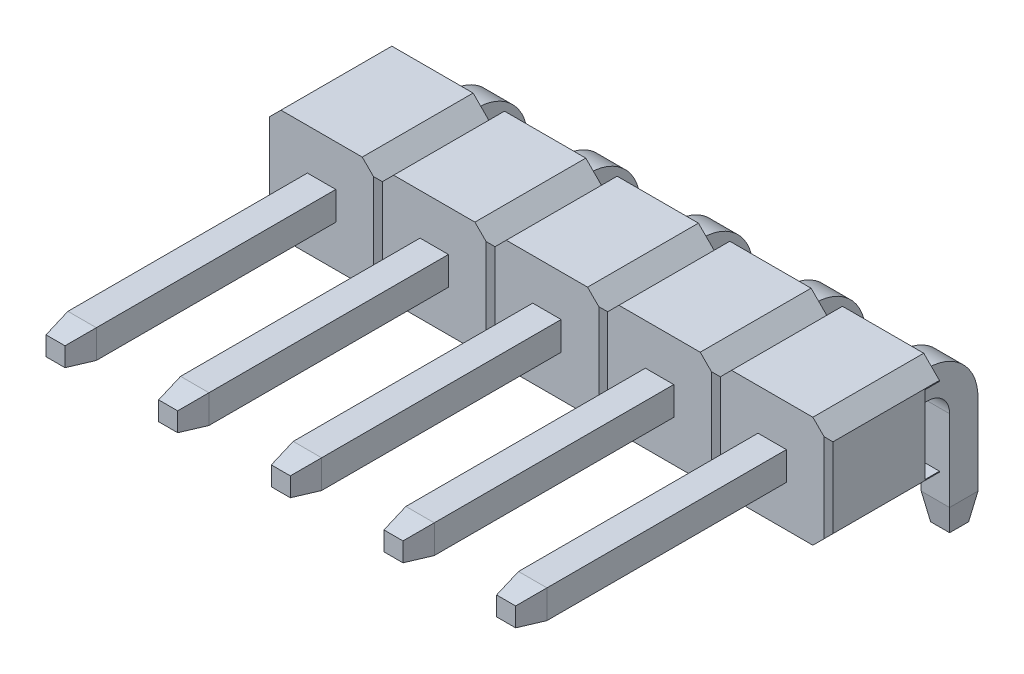
SolidWorks part; units mm, degrees
ref_plane "Front Plane" through (0, 0, 0) normal (0, 0, 1) x (1, 0, 0)
ref_plane "Top Plane" through (0, 0, 0) normal (0, 1, 0) x (1, 0, 0)
ref_plane "Right Plane" through (0, 0, 0) normal (1, 0, 0) x (0, 0, -1)
sketch "Sketch1" plane through (0, 0, 0) normal (0, 0, 1) x (1, 0, 0)
  line L0 (-1.27, 0.8964) -> (-0.9164, 1.25)
  line L1 (-0.9164, 1.25) -> (0.9164, 1.25)
  line L2 (-1.27, 0.8964) -> (-1.27, -0.8964)
  line L3 (-0.9164, -1.25) -> (0.9164, -1.25)
  line L4 (1.27, 0.8964) -> (1.27, -0.8964)
  line L5 (-1.27, -0.8964) -> (-0.9164, -1.25)
  line L6 (0.9164, -1.25) -> (1.27, -0.8964)
  line L7 (1.27, 0.8964) -> (0.9164, 1.25)
  point P0 (1.27, -1.25)
  point P7 (-1.27, 1.25)
  point P10 (-1.27, -1.25)
  point P15 (1.27, 1.25)
  dimension "D5" = 0.25
  dimension "D1" = 2.54
  dimension "D2" = 2.5
  dimension "D3" = 1.27
  dimension "D4" = 1.25
  dimension "D6" = 0.25
  dimension "D7" = 0.25
  dimension "D8" = 0.25
extrude "Extrude1" add sketch "Sketch1" along normal blind 1.25 and the other way blind 1.25
sketch "Sketch4" plane through (0, 0, 0) normal (0, 1, 0) x (1, 0, 0)
  line L0 (-1.27, -1.15) -> (-1.17, -1.25)
  line L1 (-1.17, -1.25) -> (-1.27, -1.25)
  line L2 (-1.27, -1.25) -> (-1.27, -1.15)
  line L3 (1.17, -1.25) -> (1.27, -1.15)
  line L4 (1.27, -1.15) -> (1.27, -1.25)
  line L5 (1.27, -1.25) -> (1.17, -1.25)
extrude "Cut-Extrude3" cut sketch "Sketch4" against normal through all and the other way through all
pattern_linear "LPattern4" count 3 spacing 2.54 along (-1, 0, 0) count 3 spacing 2.54 along (1, 0, 0) of "Extrude1", "Cut-Extrude3"
sketch "Sketch2" plane through (0, 0, 0) normal (1, 0, 0) x (0, -1, 0)
  line L1 (-0.8764, 1.25) -> (0.8764, 1.25)
  line L2 (-0.8764, 1.25) -> (-0.8764, 0.92)
  line L3 (-0.8764, 0.92) -> (0.8764, 0.92)
  line L4 (0.8764, 1.25) -> (0.8764, 0.92)
  dimension "D1" = 0.33
extrude "Cut-Extrude1" cut sketch "Sketch2" against normal through all and the other way through all
sketch "Sketch3" plane through (0, 0, 0) normal (1, 0, 0) x (0, 0, -1)
  line L0 (-7.25, 0) -> (2.75, 0)
  line L1 (2.75, 0) -> (2.75, -3.25)
  line L2 (-1.25, -1.25) -> (1.25, -1.25) construction
  line L3 (1.25, 1.25) -> (1.25, 0.8964) construction
  dimension "D1" = 6
  dimension "D2" = 1.5
  dimension "D3" = 2
extrude "Extrude-Thin1" add sketch "Sketch3" along normal blind 0.32 and the other way blind 0.32 thin thin type mid plane wall 0.64
pattern_linear "LPattern5" count 3 spacing 2.54 along (1, 0, 0) count 3 spacing 2.54 along (-1, 0, 0) of "Extrude-Thin1"
chamfer "Chamfer2" distance 0.6 angle 10 40 edges at (0.32, 0, 7.25) (0, -0.32, 7.25) (-0.32, 0, 7.25) (0, 0.32, 7.25) (0.32, -3.25, -2.75) (0, -3.25, -3.07) (-0.32, -3.25, -2.75) (0, -3.25, -2.43) (5.4, -3.25, -2.75) (5.08, -3.25, -3.07) (4.76, -3.25, -2.75) (5.08, -3.25, -2.43) (2.86, -3.25, -2.75) (2.54, -3.25, -3.07) (2.22, -3.25, -2.75) (2.54, -3.25, -2.43) (-4.76, -3.25, -2.75) (-5.08, -3.25, -3.07) (-5.4, -3.25, -2.75) (-5.08, -3.25, -2.43) (-2.22, -3.25, -2.75) (-2.54, -3.25, -3.07) (-2.86, -3.25, -2.75) (-2.54, -3.25, -2.43) (5.4, 0, 7.25) (5.08, -0.32, 7.25) (4.76, 0, 7.25) (5.08, 0.32, 7.25) (2.86, 0, 7.25) (2.54, -0.32, 7.25) (2.22, 0, 7.25) (2.54, 0.32, 7.25) (-2.22, 0, 7.25) (-2.54, -0.32, 7.25) (-2.86, 0, 7.25) (-2.54, 0.32, 7.25) (-4.76, 0, 7.25) (-5.08, -0.32, 7.25) (-5.4, 0, 7.25) (-5.08, 0.32, 7.25) first distance on face at (0.32, 0, 4.25) first distance on face at (0, -0.32, 4.25) first distance on face at (-0.32, 0, 4.25) first distance on face at (0, 0.32, 4.25) first distance on face at (0.32, -1.0833, -2.14) first distance on face at (0, -1.465, -3.07) first distance on face at (-0.32, -1.0833, -2.14) first distance on face at (0, -1.785, -2.43) first distance on face at (5.4, -1.0833, -2.14) first distance on face at (5.08, -1.465, -3.07) first distance on face at (4.76, -1.0833, -2.14) first distance on face at (5.08, -1.785, -2.43) first distance on face at (2.86, -1.0833, -2.14) first distance on face at (2.54, -1.465, -3.07) first distance on face at (2.22, -1.0833, -2.14) first distance on face at (2.54, -1.785, -2.43) first distance on face at (-4.76, -1.0833, -2.14) first distance on face at (-5.08, -1.465, -3.07) first distance on face at (-5.4, -1.0833, -2.14) first distance on face at (-5.08, -1.785, -2.43) first distance on face at (-2.22, -1.0833, -2.14) first distance on face at (-2.54, -1.465, -3.07) first distance on face at (-2.86, -1.0833, -2.14) first distance on face at (-2.54, -1.785, -2.43) first distance on face at (5.4, 0, 4.25) first distance on face at (5.08, -0.32, 4.25) first distance on face at (4.76, 0, 4.25) first distance on face at (5.08, 0.32, 4.25) first distance on face at (2.86, 0, 4.25) first distance on face at (2.54, -0.32, 4.25) first distance on face at (2.22, 0, 4.25) first distance on face at (2.54, 0.32, 4.25) first distance on face at (-2.22, 0, 4.25) first distance on face at (-2.54, -0.32, 4.25) first distance on face at (-2.86, 0, 4.25) first distance on face at (-2.54, 0.32, 4.25) first distance on face at (-4.76, 0, 4.25) first distance on face at (-5.08, -0.32, 4.25) first distance on face at (-5.4, 0, 4.25) first distance on face at (-5.08, 0.32, 4.25)
fillet "Fillet1" radius 0.5 5 edges at (0, -0.32, -2.43) (-5.08, -0.32, -2.43) (-2.54, -0.32, -2.43) (5.08, -0.32, -2.43) (2.54, -0.32, -2.43)
fillet "Fillet2" radius 1.14 5 edges at (0, 0.32, -3.07) (-5.08, 0.32, -3.07) (-2.54, 0.32, -3.07) (2.54, 0.32, -3.07) (5.08, 0.32, -3.07)
ref_plane "Board Plane" through (0, -1.5, 0) normal (0, 1, 0) x (-1, 0, 0)
sketch "Component_Outline" plane through (0, -1.5, 0) normal (0, 1, 0) x (-1, 0, 0)
  line L0 (6.35, 1.15) -> (6.35, -1.25)
  line L1 (6.35, -1.25) -> (5.4, -1.25)
  line L2 (5.9964, -1.25) -> (4.1636, -1.25) construction
  line L3 (5.4, -0.92) -> (5.4, -1.93) construction
  line L4 (5.4, -1.25) -> (5.4, -3.07)
  line L5 (5.4, -3.07) -> (-5.4, -3.07)
  line L6 (-5.4, -3.07) -> (-5.4, -1.25)
  line L7 (-4.1636, -1.25) -> (-5.9964, -1.25) construction
  line L8 (-5.4, -0.92) -> (-5.4, -1.93) construction
  line L9 (-5.4, -1.25) -> (-6.35, -1.25)
  line L10 (-6.35, -1.25) -> (-6.35, 1.15)
  line L11 (-6.35, 1.15) -> (-6.25, 1.25)
  line L12 (-6.25, 1.25) -> (-3.91, 1.25)
  line L13 (-3.91, 1.25) -> (-3.81, 1.15)
  line L14 (-3.81, 1.15) -> (-3.71, 1.25)
  line L15 (-3.71, 1.25) -> (-1.37, 1.25)
  line L16 (-1.37, 1.25) -> (-1.27, 1.15)
  line L17 (-1.27, 1.15) -> (-1.17, 1.25)
  line L18 (-1.17, 1.25) -> (1.17, 1.25)
  line L19 (1.17, 1.25) -> (1.27, 1.15)
  line L20 (1.27, 1.15) -> (1.37, 1.25)
  line L21 (1.37, 1.25) -> (3.71, 1.25)
  line L22 (3.71, 1.25) -> (3.81, 1.15)
  line L23 (3.81, 1.15) -> (3.91, 1.25)
  line L24 (3.91, 1.25) -> (6.25, 1.25)
  line L25 (6.25, 1.25) -> (6.35, 1.15)
  line L26 (-5.2942, -2.5358) -> (-4.8658, -2.9642) construction
  line L30 (-5.2942, -2.9642) -> (-4.8658, -2.9642)
  line L31 (-5.2942, -2.5358) -> (-5.2942, -2.9642)
  line L32 (-4.8658, -2.5358) -> (-5.2942, -2.5358)
  line L33 (-4.8658, -2.9642) -> (-4.8658, -2.5358)
  line L34 (-5.2942, -2.9642) -> (-4.8658, -2.9642) construction
  line L35 (-5.2942, -2.5358) -> (-5.2942, -2.9642) construction
  line L36 (-4.8658, -2.5358) -> (-5.2942, -2.5358) construction
  line L37 (-4.8658, -2.9642) -> (-4.8658, -2.5358) construction
  point P52 (-5.08, -2.75)
  dimension "D1" = 0
